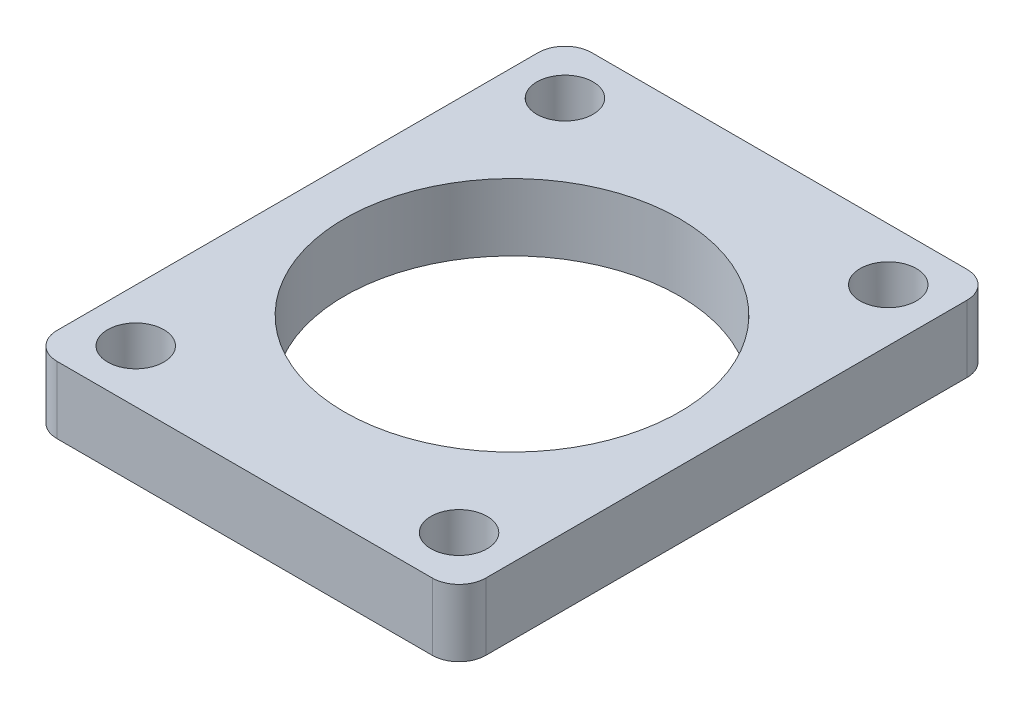
SolidWorks part; units mm, degrees
ref_plane "Front Plane" through (0, 0, 0) normal (0, 0, 1) x (1, 0, 0)
ref_plane "Top Plane" through (0, 0, 0) normal (0, 1, 0) x (1, 0, 0)
ref_plane "Right Plane" through (0, 0, 0) normal (1, 0, 0) x (0, 0, -1)
sketch "Sketch1" plane through (0, 0, 0) normal (0, 1, 0) x (1, 0, 0)
  line L1 (-20.32, 25.3365) -> (20.32, 25.3365)
  line L2 (-20.32, 25.3365) -> (-20.32, -25.3365)
  line L3 (-20.32, -25.3365) -> (20.32, -25.3365)
  line L4 (20.32, 25.3365) -> (20.32, -25.3365)
  line L5 (-20.32, 25.3365) -> (20.32, -25.3365) construction
  line L6 (-20.32, -25.3365) -> (20.32, 25.3365) construction
  circle A0 centre (0, 0) radius 15.875
  point P0 (0, 0)
  dimension "D3" = 31.75
  dimension "D1" = 40.64
  dimension "D2" = 50.673
extrude "Boss-Extrude1" add sketch "Sketch1" along normal blind 6.35
sketch "Sketch2" plane through (0, 6.35, 0) normal (0, 1, 0) x (1, 0, 0)
  line L0 (-15.32, 25.3365) -> (-15.32, 20.3365) construction
  line L1 (20.32, 25.3365) -> (-20.32, 25.3365) construction
  line L2 (-15.32, 20.3365) -> (-20.32, 20.3365) construction
  line L3 (-20.32, 25.3365) -> (-20.32, -25.3365) construction
  line L4 (0, 25.3365) -> (0, -25.3365) construction
  line L5 (-20.32, -25.3365) -> (20.32, -25.3365) construction
  line L6 (20.32, 0) -> (-20.32, 0) construction
  line L7 (20.32, -25.3365) -> (20.32, 25.3365) construction
  circle A0 centre (-15.32, 20.3365) radius 2.665
  circle A1 centre (15.32, 20.3365) radius 2.665
  circle A2 centre (15.32, -20.3365) radius 2.665
  circle A3 centre (-15.32, -20.3365) radius 2.665
  dimension "D1" = 5.33
  dimension "D2" = 5
extrude "Cut-Extrude1" cut sketch "Sketch2" against normal up to next
fillet "Fillet1" radius 2.54 4 edges at (20.32, 3.175, -25.3365) (-20.32, 3.175, -25.3365) (20.32, 3.175, 25.3365) (-20.32, 3.175, 25.3365)
